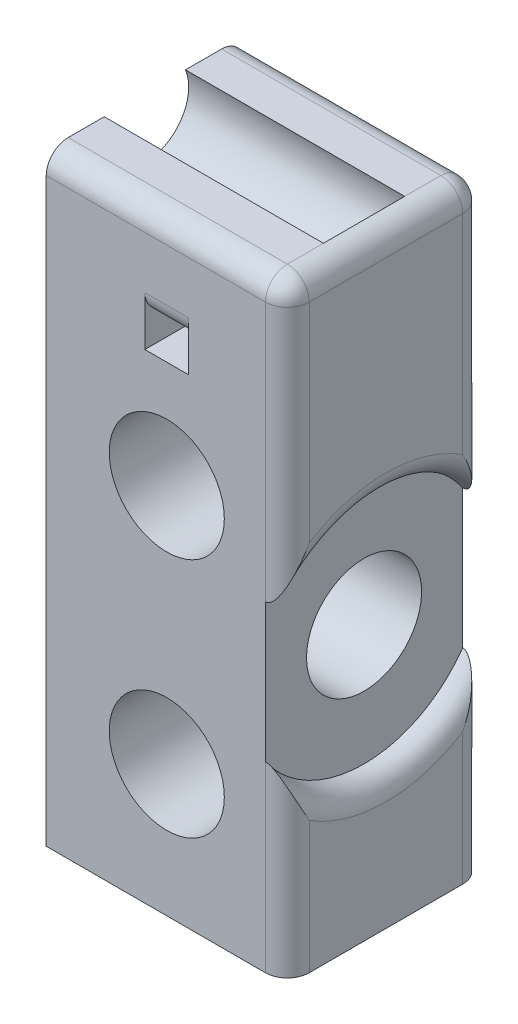
SolidWorks part; units mm, degrees
material "ABS generico"
ref_plane "Piano frontale" through (0, 0, 0) normal (0, 0, 1) x (1, 0, 0)
ref_plane "Piano superiore" through (0, 0, 0) normal (0, 1, 0) x (1, 0, 0)
ref_plane "Piano destro" through (0, 0, 0) normal (1, 0, 0) x (0, 0, -1)
sketch "Sketch1" plane through (0, 0, 0) normal (0, 0, 1) x (1, 0, 0)
  line L0 (0, 0) -> (0, 55)
  line L1 (0, 55) -> (22, 55)
  line L2 (22, 55) -> (22, 0)
  line L3 (22, 0) -> (0, 0)
  line L4 (11, 55) -> (11, 0) construction
  line L6 (13, 43.75) -> (9, 43.75)
  line L7 (13, 43.75) -> (13, 46.25)
  line L8 (13, 46.25) -> (9, 46.25)
  line L9 (9, 43.75) -> (9, 46.25)
  line L10 (13, 43.75) -> (9, 46.25) construction
  line L11 (13, 46.25) -> (9, 43.75) construction
  circle A0 centre (11, 12) radius 5.25
  circle A1 centre (11, 34) radius 5.25
  point P11 (11, 45)
  dimension "D5" = 10.5
  dimension "D1" = 22
  dimension "D2" = 55
  dimension "D3" = 12
  dimension "D4" = 34
  dimension "D6" = 10
  dimension "D7" = 4
  dimension "D8" = 2.5
extrude "Boss-Extrude1" add sketch "Sketch1" against normal blind 18
sketch "Sketch2" plane through (0, 0, 0) normal (-1, 0, 0) x (0, 0, 1)
  line L0 (-9, 0) -> (-9, 55) construction
  line L1 (-18, 0) -> (0, 0) construction
  line L2 (-18, 55) -> (0, 55) construction
  circle A0 centre (-9, 23) radius 5.25
  dimension "D2" = 10.5
  dimension "D1" = 23
extrude "Cut-Extrude1" cut sketch "Sketch2" against normal through all
sketch "Sketch3" plane through (0, 0, 0) normal (1, 0, 0) x (0, 0, -1)
  line L0 (9, 55) -> (9, 62.8182) construction
  line L2 (18, 55) -> (0, 55) construction
  circle A0 centre (9, 53.5) radius 4
  dimension "D1" = 8
  dimension "D2" = 1.5
extrude "Cut-Extrude2" cut sketch "Sketch3" along normal blind 20
sketch "Sketch4" plane through (22, 0, 0) normal (1, 0, 0) x (0, 0, -1)
  circle A0 centre (9, 23) radius 11
  dimension "D1" = 22
extrude "Cut-Extrude3" cut sketch "Sketch4" against normal blind 2
fillet "Fillet3" radius 2 8 edges at (22, 34, -9) (22, 12, -9) (22, 8.3377, -18) (22, 8.3377, 0) (22, 42.1623, -18) (22, 42.1623, 0) (11, 55, -18) (11, 55, 0)
fillet "Fillet2" radius 2 2 edges at (11, 46.25, -18) (11, 46.25, 0)
fillet "Fillet4" radius 2 3 edges at (21.4142, 54.4142, -17.4142) (21.4142, 54.4142, -0.5858) (22, 55, -9)
